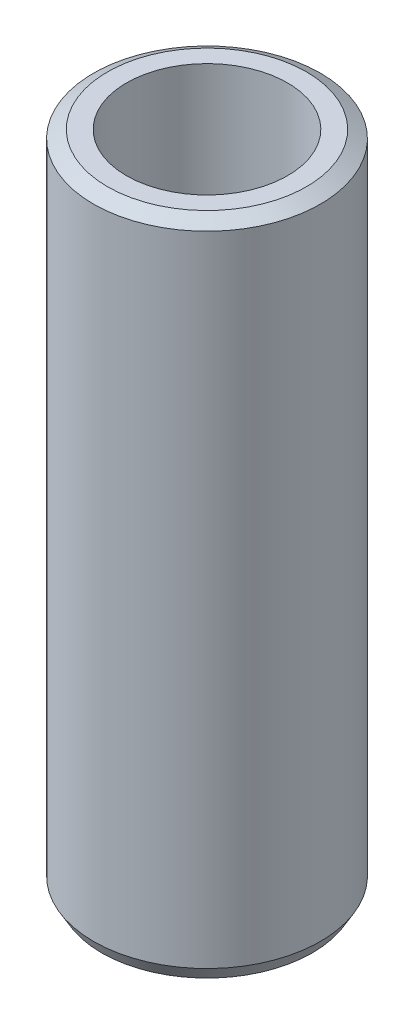
SolidWorks part; units mm, degrees
ref_plane "Front Plane" through (0, 0, 0) normal (0, 0, 1) x (1, 0, 0)
ref_plane "Top Plane" through (0, 0, 0) normal (0, 1, 0) x (1, 0, 0)
ref_plane "Right Plane" through (0, 0, 0) normal (1, 0, 0) x (0, 0, -1)
sketch "Sketch1" plane through (0, 0, 0) normal (0, 1, 0) x (1, 0, 0)
  circle A0 centre (0, 0) radius 30
  dimension "SHAFT_OD" = 60
extrude "Boss-Extrude1" add sketch "Sketch1" along normal blind 174.6416
sketch "Sketch2" plane through (0, 0, 0) normal (0, 1, 0) x (1, 0, 0)
  circle A0 centre (0, 0) radius 21.2861
  dimension "BORE_D" = 42.5723
extrude "Cut-Extrude1" cut sketch "Sketch2" along normal through all
chamfer "Chamfer1" distance 2.133 angle 60 2 edges at (0, 174.6416, 30) (0, 0, 30) first distance on face at (0, 174.6416, 30) first distance on face at (0, 0, 21.2861)
